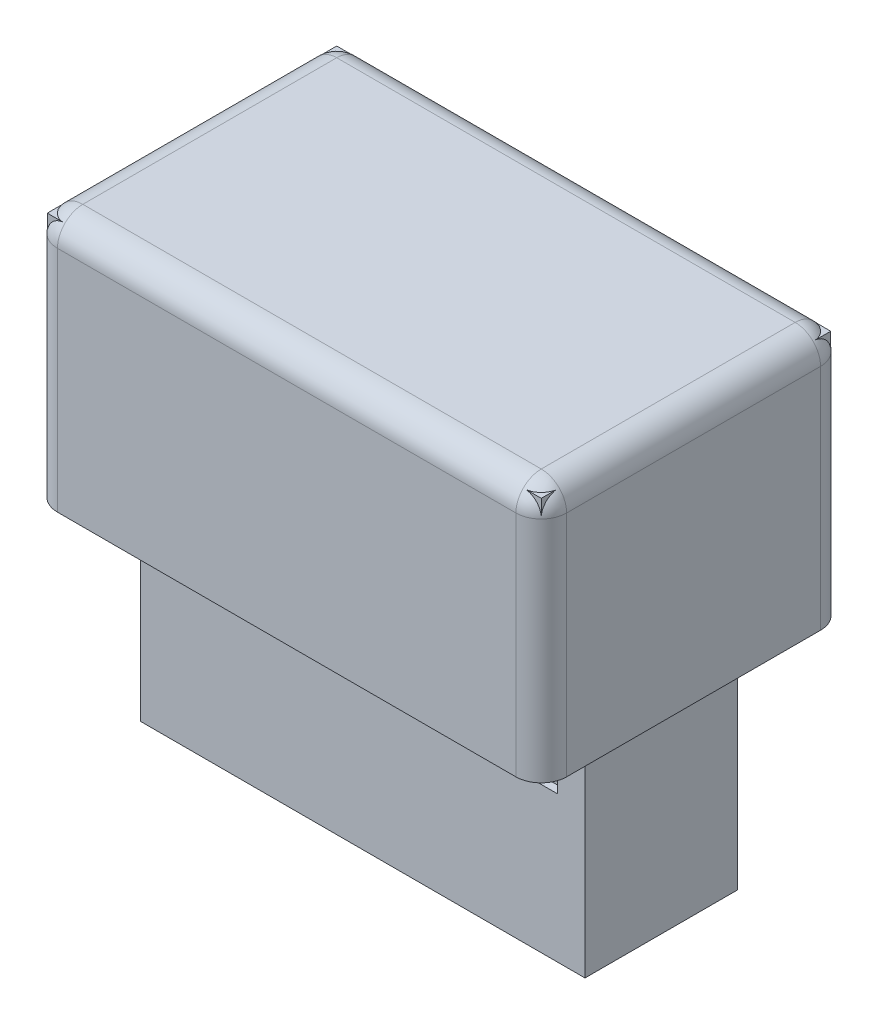
SolidWorks part; units mm, degrees
ref_plane "Front Plane" through (0, 0, 0) normal (0, 0, 1) x (1, 0, 0)
ref_plane "Top Plane" through (0, 0, 0) normal (0, 1, 0) x (1, 0, 0)
ref_plane "Right Plane" through (0, 0, 0) normal (1, 0, 0) x (0, 0, -1)
sketch "Sketch1" plane through (0, 0, 0) normal (0, 0, 1) x (1, 0, 0)
  line L1 (0, 0) -> (40.11, 0)
  line L2 (0, 0) -> (0, 20)
  line L3 (0, 20) -> (40.11, 20)
  line L4 (40.11, 0) -> (40.11, 20)
  dimension "D1" = 40.11
  dimension "D2" = 20
extrude "Boss-Extrude1" add sketch "Sketch1" along normal mid plane 24
sketch "Sketch2" plane through (0, 0, 0) normal (0, 0, 1) x (1, 0, 0)
  line L0 (0, 0) -> (40.11, 0) construction
  line L1 (2.555, 0) -> (37.555, 0)
  line L2 (2.555, 0) -> (2.555, -17)
  line L3 (2.555, -17) -> (37.555, -17)
  line L4 (37.555, 0) -> (37.555, -17)
  line L5 (40.11, 20) -> (0, 20) construction
  point P6 (20.055, 0)
  point P9 (20.055, 20)
  dimension "D1" = 37
  dimension "D2" = 35
extrude "Boss-Extrude2" add sketch "Sketch2" along normal mid plane 12
sketch "Sketch3" plane through (0, 0, 0) normal (0, 0, 1) x (1, 0, 0)
  line L0 (0, 0) -> (-3.5, 0)
  line L1 (0, 20) -> (0, 0) construction
  line L2 (2.555, -17) -> (37.555, -17) construction
  line L3 (-3.5, 0) -> (-3.5, -0.45)
  line L4 (-3.5, -0.45) -> (-4, -0.45)
  line L5 (-4.5, 0.05) -> (-4.5, 0.7)
  line L6 (0, 0) -> (0, 0.7)
  line L7 (0, 0.7) -> (-4.5, 0.7) construction
  line L8 (0, 0.7) -> (-4.5, 0.7)
  arc A0 (-4, -0.45) -> (-4.5, 0.05) centre (-4, 0.05) cw
  point P12 (-4.5, -0.45)
  dimension "D6" = 0.5
  dimension "D1" = 17
  dimension "D2" = 4.5
  dimension "D3" = 1
  dimension "D4" = 1.4
  dimension "D5" = 2.3
revolve "Revolve1" add sketch "Sketch3" angle 360 about L7
shell "Shell1" thickness 0.6 removed face at (20.055, -17, 0)
sketch "Sketch4" plane through (0, 0, 0) normal (0, 0, 1) x (1, 0, 0)
  line L0 (0, 0) -> (40.11, 0) construction
  line L1 (4.74, 0) -> (35.37, 0)
  line L2 (4.74, 0) -> (4.74, -5.52)
  line L3 (4.74, -5.52) -> (35.37, -5.52)
  line L4 (35.37, 0) -> (35.37, -5.52)
  line L5 (2.555, -17) -> (37.555, -17) construction
  point P6 (20.055, -5.52)
  point P9 (20.055, -17)
  dimension "D1" = 30.63
  dimension "D2" = 11.48
extrude "Cut-Extrude1" cut sketch "Sketch4" against normal up to next and the other way up to next
ref_plane "Plane1" through (20.055, 0, 0) normal (-1, 0, 0) x (0, 0, 1)
sketch "Sketch5" plane through (20.055, 0, 0) normal (-1, 0, 0) x (0, 0, 1)
  line L0 (11.4, 19.4) -> (-11.4, 19.4) construction
  line L1 (-5.49, 19.4) -> (5.49, 19.4)
  line L2 (-5.49, 19.4) -> (-5.49, -5.52)
  line L3 (-5.49, -5.52) -> (5.49, -5.52)
  line L4 (5.49, 19.4) -> (5.49, -5.52)
  line L5 (12, 20) -> (-12, 20) construction
  point P6 (0, -5.52)
  dimension "D1" = 10.98
  dimension "D2" = 25.52
extrude "Boss-Extrude3" add sketch "Sketch5" along normal blind 1.74 from offset 9.13
mirror "Mirror1" about plane through (20.055, 0, 0) normal (-1, 0, 0) of "Boss-Extrude3"
fillet "Fillet1" radius 2 8 edges at (40.11, 20, 0) (20.055, 20, 12) (0, 20, 0) (20.055, 20, -12) (40.11, 10, 12) (40.11, 10, -12) (0, 10, 12) (0, 10, -12)
